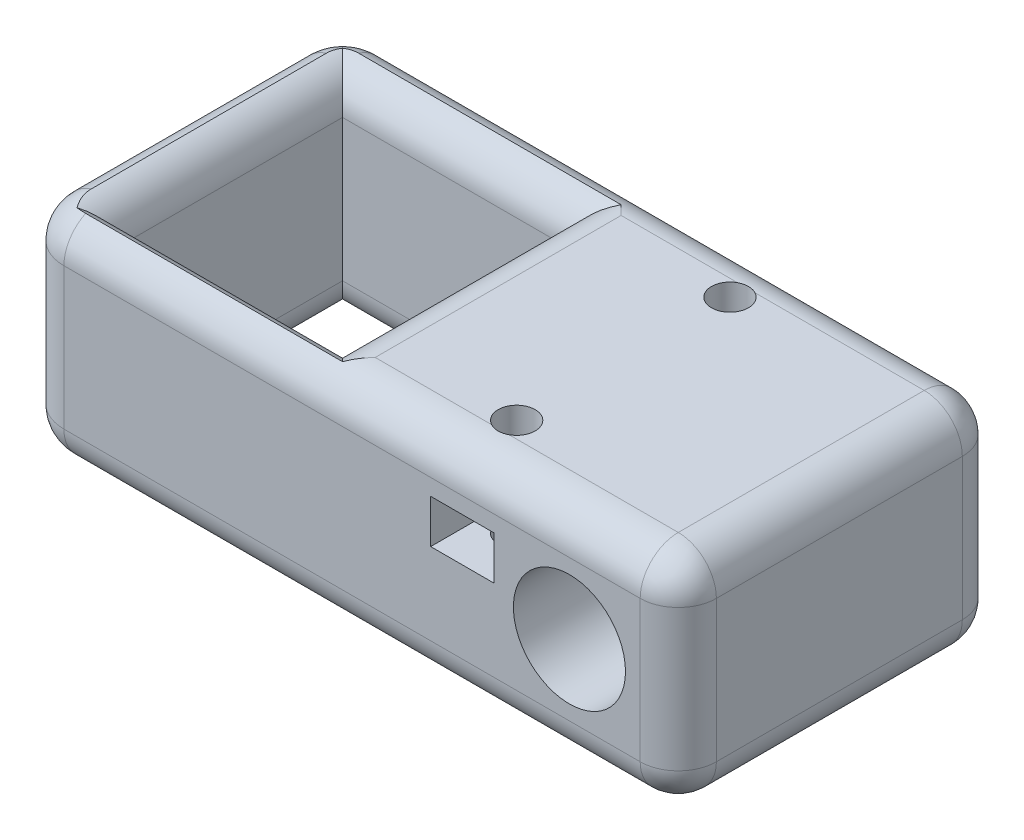
SolidWorks part; units mm, degrees
ref_plane "Front" through (0, 0, 0) normal (0, 0, 1) x (1, 0, 0)
ref_plane "Top" through (0, 0, 0) normal (0, 1, 0) x (1, 0, 0)
ref_plane "Right" through (0, 0, 0) normal (1, 0, 0) x (0, 0, -1)
sketch "Sketch1" plane through (0, 0, 0) normal (0, 1, 0) x (1, 0, 0)
  line L1 (0, 0) -> (20.6, 0)
  line L2 (0, 0) -> (0, 20.6)
  line L3 (0, 20.6) -> (20.6, 20.6)
  line L4 (20.6, 0) -> (20.6, 20.6)
  line L5 (-1, -4) -> (16.6, -4)
  line L6 (-5, 0) -> (-5, 21.6)
  line L7 (-1, 25.6) -> (20.6, 25.6)
  line L9 (55.45, -4) -> (55.45, 25.6)
  line L10 (55.45, 25.6) -> (20.6, 25.6)
  line L11 (40.45, -4) -> (40.45, 16) construction
  line L12 (40.45, 16) -> (50.45, 16) construction
  line L13 (50.45, 16) -> (50.45, -4) construction
  line L14 (16.6, -4) -> (55.45, -4)
  arc A2 (-5, 0) -> (-1, -4) centre (-1, 0) ccw
  arc A3 (-5, 21.6) -> (-1, 25.6) centre (-1, 21.6) cw
  point P10 (9.8, 25.6)
  dimension "D5" = 5
  dimension "D1" = 5
  dimension "D2" = 20.6
  dimension "D3" = 5
  dimension "D4" = 4
  dimension "D6" = 10
  dimension "D7" = 20
  dimension "D8" = 19.85
extrude "Boss-Extrude1" add sketch "Sketch1" along normal blind 20
sketch "Sketch2" plane through (0, 0, 4) normal (0, 0, 1) x (1, 0, 0)
  line L0 (40.45, 0) -> (50.45, 0) construction
  line L1 (40.45, 0) -> (50.45, 0)
  line L2 (55.45, 20) -> (55.45, 0) construction
  circle A0 centre (45.45, 10) radius 5.15
  point P5 (45.45, 0)
  point P9 (55.45, 10)
  dimension "D1" = 10.3
extrude "Cut-Extrude1" cut sketch "Sketch2" against normal blind 20 contours A0 region at (45.45, 10, 4)
fillet "Fillet1" radius 3.5 22 edges at (55.45, 10, -25.6) (20.6, 0, -10.3) (10.3, 0, 0) (0, 0, -10.3) (10.3, 0, -20.6) (-3.8284, 0, -24.4284) (-5, 0, -10.8) (-3.8284, 0, 2.8284) (27.225, 0, 4) (55.45, 0, -10.8) (27.225, 0, -25.6) (10.3, 20, 0) (20.6, 20, -10.3) (10.3, 20, -20.6) (0, 20, -10.3) (55.45, 20, -10.8) (27.225, 20, 4) (-3.8284, 20, 2.8284) (-5, 20, -10.8) (-3.8284, 20, -24.4284) (27.225, 20, -25.6) (55.45, 10, 4)
ref_plane "Plane1" through (0, 15, 0) normal (0, 1, 0) x (1, 0, 0)
sketch "Sketch3" plane through (0, 15, 0) normal (0, 1, 0) x (1, 0, 0)
  line L0 (16.6, -4) -> (55.45, -4) construction
  line L2 (32.7, 22.2743) -> (32.7, 18.9257)
  line L3 (32.7, 18.9257) -> (35.6, 17.2514)
  line L4 (35.6, 17.2514) -> (38.5, 18.9257)
  line L5 (38.5, 18.9257) -> (38.5, 22.0295)
  line L7 (35.6, 4.3486) -> (32.7, 2.6743)
  line L8 (32.7, 2.6743) -> (32.7, -0.8037)
  line L11 (38.5, -0.4295) -> (38.5, 2.6743)
  line L12 (38.5, 2.6743) -> (35.6, 4.3486)
  line L13 (55.45, 25.6) -> (20.6, 25.6) construction
  line L14 (20.6, 0) -> (20.6, 20.6) construction
  line L15 (32.7, 22.2743) -> (32.7, 26.9976)
  line L16 (32.7, 26.9976) -> (38.5, 26.9976)
  line L17 (38.5, 26.9976) -> (38.5, 22.0295)
  line L18 (38.5, -0.4295) -> (38.5, -7.27)
  line L19 (38.5, -7.27) -> (32.7, -7.27)
  line L20 (32.7, -7.27) -> (32.7, -0.8037)
  line L22 (32.9121, -0.7967) -> (35.7121, -2.4133) [skipped]
  line L23 (35.8121, -2.2262) -> (38.6121, -0.6096) [skipped]
  line L24 (38.2879, 22.3967) -> (35.4879, 24.0133) [skipped]
  line L25 (35.3879, 23.8262) -> (32.5879, 22.2096) [skipped]
  circle A0 centre (35.6, 20.6) radius 2.8 construction
  circle A1 centre (35.6, 1) radius 2.9 construction
  dimension "D1" = 5.8
  dimension "D2" = 5
  dimension "D3" = 5
  dimension "D4" = 15
extrude "Cut-Extrude2" cut sketch "Sketch3" against normal blind 4
sketch "Sketch4" plane through (0, 20, 0) normal (0, 1, 0) x (1, 0, 0)
  circle A0 centre (35.6, 20.6) radius 1.7
  circle A1 centre (35.6, 1) radius 1.7
  dimension "D1" = 3.4
extrude "Cut-Extrude3" cut sketch "Sketch4" against normal through all
